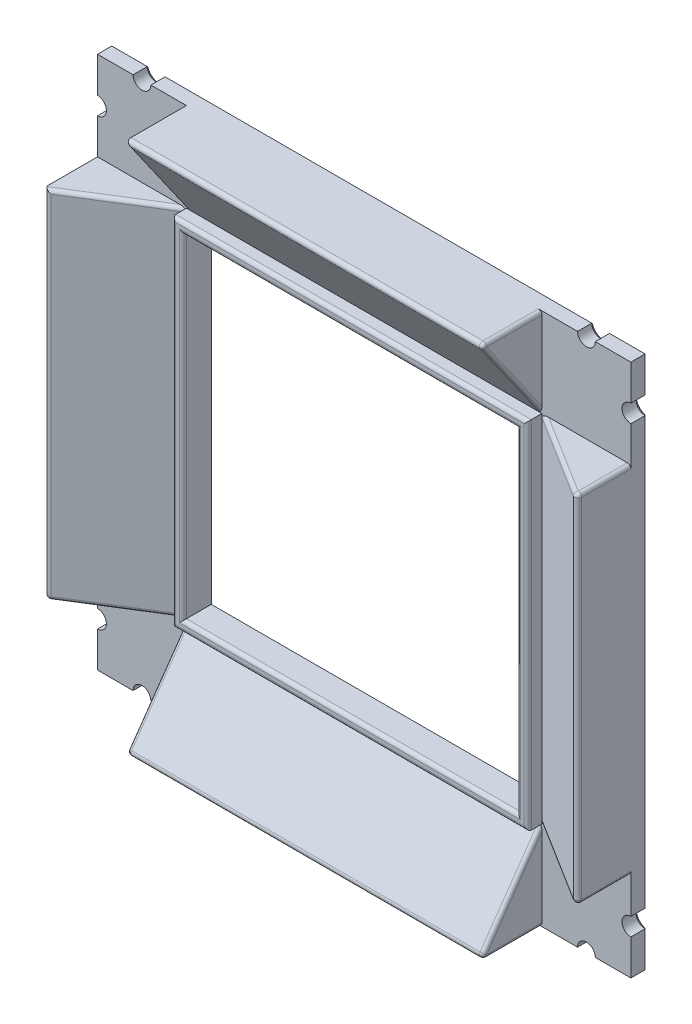
SolidWorks part; units mm, degrees
ref_plane "Front Plane" through (0, 0, 0) normal (0, 0, 1) x (1, 0, 0)
ref_plane "Top Plane" through (0, 0, 0) normal (0, 1, 0) x (1, 0, 0)
ref_plane "Right Plane" through (0, 0, 0) normal (1, 0, 0) x (0, 0, -1)
sketch "Sketch1" plane through (0, 0, 0) normal (0, 0, 1) x (1, 0, 0)
  line L1 (-50, 50) -> (50, 50)
  line L2 (-50, 50) -> (-50, -50)
  line L3 (-50, -50) -> (50, -50)
  line L4 (50, 50) -> (50, -50)
  line L5 (-50, 50) -> (50, -50) construction
  line L6 (-50, -50) -> (50, 50) construction
  line L7 (-75, 75) -> (75, 75)
  line L8 (-75, 75) -> (-75, -75)
  line L9 (-75, -75) -> (75, -75)
  line L10 (75, 75) -> (75, -75)
  line L11 (-75, 75) -> (75, -75) construction
  line L12 (-75, -75) -> (75, 75) construction
  point P0 (0, 0)
  point P5 (0, 0)
extrude "Boss-Extrude1" add sketch "Sketch1" along normal blind 5
sketch "Sketch3" plane through (50, 0, 0) normal (-1, 0, 0) x (0, 0, 1)
  line L2 (5, -50) -> (5, -75)
  line L3 (5, -50) -> (22.5052, -75)
  line L4 (5, -75) -> (22.5052, -75)
  line L7 (5, 50) -> (5, 75)
  line L8 (5, 75) -> (22.5052, 75)
  line L9 (5, 50) -> (22.5052, 75)
  dimension "D1" = 35
extrude "Boss-Extrude2" add sketch "Sketch3" along normal up to surface (100 mm away) contours L2 L4 L3 | L7 L9 L8 up to face at (-50, 0, 2.5)
sketch "Sketch4" plane through (0, -50, 0) normal (0, 1, 0) x (1, 0, 0)
  line L2 (75, -5) -> (75, -20.6217)
  line L3 (50, -5) -> (75, -20.6217)
  line L6 (-50, -5) -> (-75, -5)
  line L7 (-50, -5) -> (-75, -20.6217)
  line L8 (-75, -5) -> (-75, -20.6217)
  line L9 (50, -5) -> (75, -5)
  dimension "D1" = 32
extrude "Boss-Extrude3" add sketch "Sketch4" along normal up to surface (100 mm away) up to face at (0, 50, 2.5)
sketch "Sketch5" plane through (0, 0, 0) normal (0, 0, -1) x (-1, 0, 0)
  line L0 (50, -50) -> (-50, -50) construction
  line L1 (50, 50) -> (50, -50) construction
  line L2 (-50, 50) -> (50, 50) construction
  line L3 (-50, -50) -> (-50, 50) construction
  line L4 (50, -50) -> (-50, -50)
  line L5 (50, 50) -> (50, -50)
  line L6 (-50, 50) -> (50, 50)
  line L7 (-50, -50) -> (-50, 50)
  line L8 (-47, 47) -> (47, 47)
  line L9 (47, 47) -> (47, -47)
  line L10 (47, -47) -> (-47, -47)
  line L11 (-47, -47) -> (-47, 47)
  dimension "D1" = 3
extrude "Boss-Extrude4" add sketch "Sketch5" against normal blind 9
sketch "Sketch6" plane through (0, 0, 5) normal (0, 0, 1) x (1, 0, 0)
  line L0 (-75, -75) -> (-50, -75) construction
  circle A0 centre (-62.5, -75) radius 2.5
  circle A1 centre (-75, -62.5) radius 2.5
  circle A2 centre (-75, 62.5) radius 2.5
  circle A3 centre (-62.5, 75) radius 2.5
  circle A4 centre (62.5, 75) radius 2.5
  circle A5 centre (75, 62.5) radius 2.5
  circle A6 centre (75, -62.5) radius 2.5
  circle A7 centre (62.5, -75) radius 2.5
extrude "Cut-Extrude1" cut sketch "Sketch6" against normal through all
chamfer "Chamfer1" distance 1 angle 45 24 edges at (-75, 0, 0) (-75, -70, 0) (0, 75, 0) (-70, 75, 0) (75, 0, 0) (75, 70, 0) (-72.5, -62.5, 0) (-72.5, 62.5, 0) (-62.5, 72.5, 0) (62.5, 72.5, 0) (72.5, 62.5, 0) (72.5, -62.5, 0) (62.5, -72.5, 0) (-62.5, -72.5, 0) (-70, -75, 0) (-75, 70, 0) (70, 75, 0) (75, -70, 0) (47, 0, 0) (0, 47, 0) (-47, 0, 0) (0, -47, 0) (0, -75, 0) (70, -75, 0)
fillet "Fillet1" radius 1 26 edges at (0, 50, 9) (50, 0, 9) (0, -50, 9) (-50, 0, 9) (0, 47, 9) (-47, 0, 9) (0, -47, 9) (47, 0, 9) (50, -62.5, 13.7526) (-50, -75, 13.7526) (-50, -62.5, 13.7526) (-50, 62.5, 13.7526) (-62.5, 50, 12.8109) (50, 75, 13.7526) (50, 62.5, 13.7526) (62.5, 50, 12.8109) (75, 50, 12.8109) (75, -50, 12.8109) (62.5, -50, 12.8109) (-75, -50, 12.8109) (-62.5, -50, 12.8109) (0, 75, 22.5052) (75, 0, 20.6217) (0, -75, 22.5052) (-75, 0, 20.6217) (50, -75, 13.7526)
